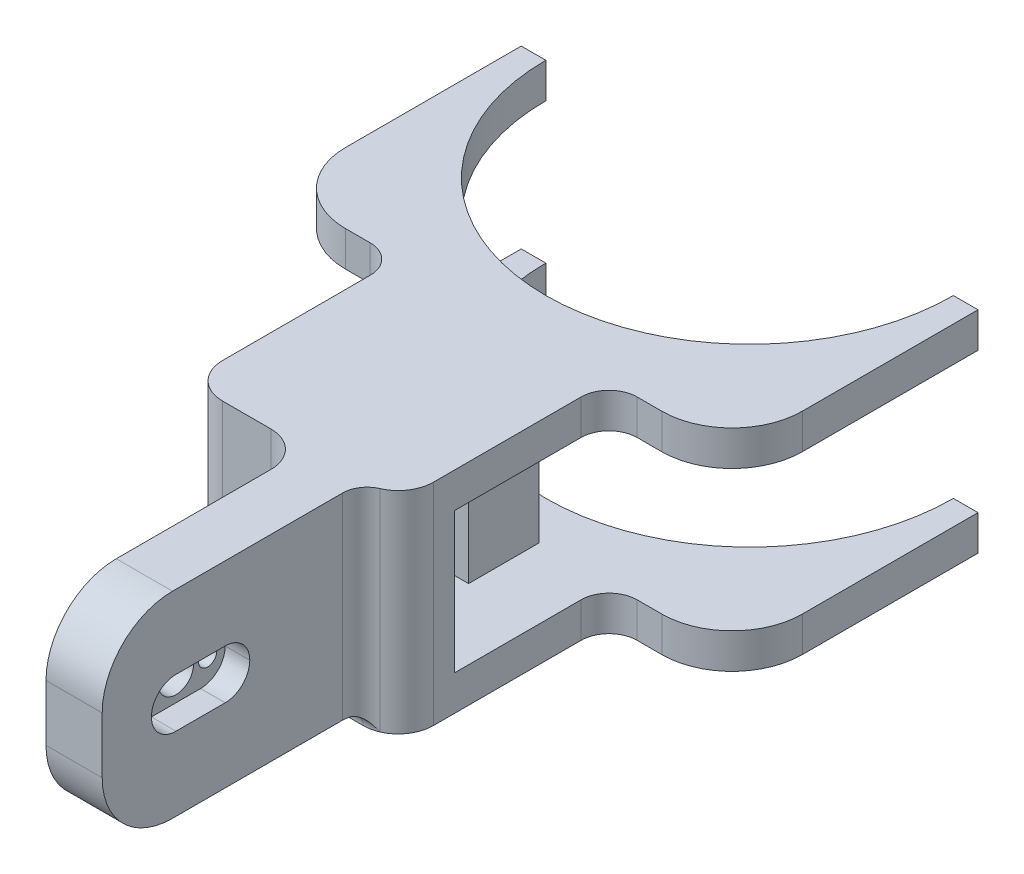
SolidWorks part; units mm, degrees
ref_plane "Front Plane" through (0, 0, 0) normal (0, 0, 1) x (1, 0, 0)
ref_plane "Top Plane" through (0, 0, 0) normal (0, 1, 0) x (1, 0, 0)
ref_plane "Right Plane" through (0, 0, 0) normal (1, 0, 0) x (0, 0, -1)
sketch "Sketch1" plane through (0, 0, 0) normal (0, 0, 1) x (1, 0, 0)
  line L1 (-14, 5) -> (-6, 5)
  line L2 (-14, 5) -> (-14, -23)
  line L3 (-14, -23) -> (-6, -23)
  line L4 (-6, 5) -> (-6, -23)
  dimension "D2" = 8
  dimension "D3" = 28
extrude "Boss-Extrude1" add sketch "Sketch1" along normal blind 32 and the other way blind 5
sketch "Sketch2" plane through (-14, 0, 0) normal (-1, 0, 0) x (0, 0, 1)
  line L0 (-5, 5) -> (32, 5) construction
  line L1 (32, 5) -> (32, -23) construction
  circle A0 centre (18, -9) radius 2.5
  dimension "D1" = 5
  dimension "D2" = 14
  dimension "D3" = 14
extrude "Cut-Extrude1" cut sketch "Sketch2" against normal blind 32
fillet "Fillet1" radius 10 2 edges at (-10, -23, 32) (-10, 5, 32)
sketch "Sketch3" plane through (-14, 0, 0) normal (-1, 0, 0) x (0, 0, 1)
  circle A0 centre (13.5, -9.0421) radius 1.3
  circle A1 centre (22.5, -8.7477) radius 1.3
  circle A2 centre (18, -9) radius 2.5 construction
  dimension "D1" = 2.6
  dimension "D2" = 4.5
  dimension "D3" = 9
extrude "Cut-Extrude2" cut sketch "Sketch3" against normal blind 32
sketch "Sketch4" plane through (-6, 0, 0) normal (1, 0, 0) x (0, 0, -1)
  line L3 (-25, -5.5) -> (-11, -5.5)
  line L4 (-25, -5.5) -> (-25, -12.5)
  line L5 (-25, -12.5) -> (-11, -12.5)
  line L6 (-11, -5.5) -> (-11, -12.5)
  line L7 (-25, -5.5) -> (-11, -12.5) construction
  line L8 (-25, -12.5) -> (-11, -5.5) construction
  point P0 (-18, -9)
  dimension "D1" = 14
  dimension "D2" = 7
extrude "Cut-Extrude3" cut sketch "Sketch4" against normal blind 3.5
fillet "Fillet3" radius 3.5 4 edges at (-7.75, -5.5, 11) (-7.75, -12.5, 11) (-7.75, -12.5, 25) (-7.75, -5.5, 25)
sketch "Sketch8" plane through (-14, 0, 0) normal (-1, 0, 0) x (0, 0, 1)
  line L0 (-10, 0) -> (-5, 0)
  line L1 (-5, 0) -> (-5, -23)
  line L2 (-5, -23) -> (-10, -5.5)
  line L3 (-10, -5.5) -> (-10, 0)
  line L5 (-5, 5) -> (-5, -23) construction
  line L6 (-5, 0) -> (-5, -23)
  line M12 (-5, 5) -> (-5, -23)
  dimension "D1" = 5
extrude "Boss-Extrude2" add sketch "Sketch8" against normal up to surface (8 mm away) contours L3 L2 L1 L0 M12 region at (-14, -8.0205, -6.9883) up to face at (-6, -9, 18)
sketch "Sketch9" plane through (0, 5, 0) normal (0, 1, 0) x (1, 0, 0)
  line L0 (-6, 5) -> (-14, 5) construction
  line L1 (-0.8695, 5) -> (-30.8695, 5)
  line L2 (-0.8695, 5) -> (-0.8695, 35)
  line L3 (-0.8695, 35) -> (-30.8695, 35)
  line L4 (-30.8695, 5) -> (-30.8695, 35)
  line L5 (-0.8695, 5) -> (-30.8695, 35) construction
  line L6 (-0.8695, 35) -> (-30.8695, 5) construction
  point P4 (-15.8695, 20)
  dimension "D1" = 30
  dimension "D2" = 30
extrude "Boss-Extrude3" add sketch "Sketch9" against normal blind 5 contours L2 L1 L4 L3
sketch "Sketch10" plane through (0, 5, 0) normal (0, 1, 0) x (1, 0, 0)
  line L1 (-30.8695, 5) -> (-0.8695, 5)
  line L2 (-30.8695, 5) -> (-30.8695, 35)
  line L3 (-30.8695, 35) -> (-0.8695, 35)
  line L4 (-0.8695, 5) -> (-0.8695, 35)
  line L5 (-30.8695, 5) -> (-0.8695, 35) construction
  line L6 (-30.8695, 35) -> (-0.8695, 5) construction
  point P4 (-15.8695, 20)
extrude "Boss-Extrude4" add sketch "Sketch10" against normal blind 5 from offset 25 offset against normal yes
sketch "Sketch11" plane through (0, 5, 0) normal (0, 1, 0) x (1, 0, 0)
  line L0 (-0.8695, 5) -> (-0.8695, 35) construction
  line L1 (-30.8695, 5) -> (-0.8695, 5)
  line L2 (-30.8695, 5) -> (-30.8695, 13)
  line L3 (-30.8695, 13) -> (-0.8695, 13)
  line L4 (-0.8695, 5) -> (-0.8695, 13)
  line L5 (-30.8695, 5) -> (-0.8695, 13) construction
  line L6 (-30.8695, 13) -> (-0.8695, 5) construction
  point P4 (-15.8695, 9)
  dimension "D1" = 8
extrude "Boss-Extrude5" add sketch "Sketch11" against normal blind 30
fillet "Fillet4" radius 5 2 edges at (-30.8695, -10, -5) (-0.8695, -10, -5)
fillet "Fillet5" radius 5 1 edges at (-14, -9, -5)
fillet "Fillet6" radius 3.5 1 edges at (-6, -9, -5)
sketch "Sketch12" plane through (0, 5, 0) normal (0, 1, 0) x (1, 0, 0)
  line L0 (-0.8695, 35) -> (-30.8695, 35) construction
  line L1 (-20.8695, 35) -> (-10.8695, 35)
  line L2 (-20.8695, 35) -> (-20.8695, 25)
  line L3 (-20.8695, 25) -> (-10.8695, 25)
  line L4 (-10.8695, 35) -> (-10.8695, 25)
  line L5 (-20.8695, 35) -> (-10.8695, 25) construction
  line L6 (-20.8695, 25) -> (-10.8695, 35) construction
  point P4 (-15.8695, 30)
  point P7 (-15.8695, 35)
  dimension "D1" = 10
  dimension "D2" = 10
extrude "Boss-Extrude6" add sketch "Sketch12" against normal blind 30
sketch "Sketch13" plane through (0, 5, 0) normal (0, 1, 0) x (1, 0, 0)
  line L5 (-0.8695, 35) -> (-30.8695, 35) construction
  line L6 (-48.3695, 70) -> (16.6305, 70)
  line L7 (-48.3695, 70) -> (-48.3695, 35)
  line L8 (-48.3695, 35) -> (16.6305, 35)
  line L9 (16.6305, 70) -> (16.6305, 35)
  line L10 (-48.3695, 70) -> (16.6305, 35) construction
  line L11 (-48.3695, 35) -> (16.6305, 70) construction
  point P5 (-15.8695, 52.5)
  point P8 (-15.8695, 35)
  dimension "D1" = 65
  dimension "D2" = 35
extrude "Boss-Extrude7" add sketch "Sketch13" against normal blind 5
sketch "Sketch14" plane through (0, 5, 0) normal (0, 1, 0) x (1, 0, 0)
  line L1 (-48.3695, 70) -> (16.6305, 70)
  line L2 (-48.3695, 70) -> (-48.3695, 35)
  line L3 (-48.3695, 35) -> (16.6305, 35)
  line L4 (16.6305, 70) -> (16.6305, 35)
  line L5 (-48.3695, 70) -> (16.6305, 35) construction
  line L6 (-48.3695, 35) -> (16.6305, 70) construction
  point P4 (-15.8695, 52.5)
extrude "Boss-Extrude8" add sketch "Sketch14" against normal blind 5 from offset 25 offset against normal yes
sketch "Sketch15" plane through (0, 5, 0) normal (0, 1, 0) x (1, 0, 0)
  line L0 (16.6305, 70) -> (-48.3695, 70) construction
  circle A0 centre (-15.8695, 70) radius 29
  dimension "D1" = 58
extrude "Cut-Extrude7" cut sketch "Sketch15" against normal blind 43
fillet "Fillet7" radius 4 4 edges at (-0.8695, -22.5, -35) (-0.8695, 2.5, -35) (-30.8695, -22.5, -35) (-30.8695, 2.5, -35)
fillet "Fillet8" radius 10 4 edges at (-48.3695, -22.5, -35) (-48.3695, 2.5, -35) (16.6305, -22.5, -35) (16.6305, 2.5, -35)
fillet "Fillet9" radius 2 2 edges at (-4.8575, -23, -5.1035) (-12.4347, -23, -5)
